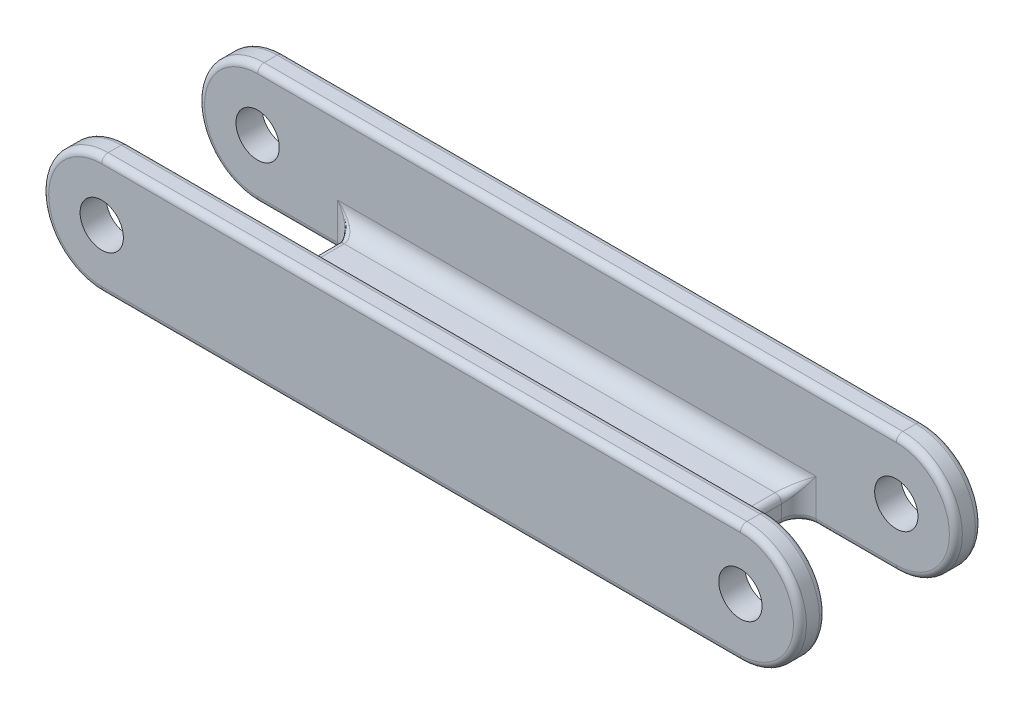
SolidWorks part; units mm, degrees
material "AISI 1020"
ref_plane "Front Plane" through (0, 0, 0) normal (0, 0, 1) x (1, 0, 0)
ref_plane "Top Plane" through (0, 0, 0) normal (0, 1, 0) x (1, 0, 0)
ref_plane "Right Plane" through (0, 0, 0) normal (1, 0, 0) x (0, 0, -1)
sketch "Sketch1" plane through (0, 0, 0) normal (1, 0, 0) x (0, 0, -1)
  line L0 (-42, 27.5) -> (-30, 27.5)
  line L1 (42, -27.5) -> (-42, -27.5)
  line L2 (42, -27.5) -> (42, 27.5)
  line L3 (42, 27.5) -> (-42, 27.5) construction
  line L4 (-42, -27.5) -> (-42, 27.5)
  line L5 (42, -27.5) -> (-42, 27.5) construction
  line L6 (42, 27.5) -> (-42, -27.5) construction
  line L7 (-30, 27.5) -> (-30, -15.5)
  line L8 (-30, -15.5) -> (30, -15.5)
  line L9 (30, -15.5) -> (30, 27.5)
  line L10 (30, 27.5) -> (42, 27.5)
  point P0 (0, 0)
  dimension "D1" = 12
  dimension "D2" = 12
  dimension "D3" = 60
  dimension "D4" = 55
extrude "Boss-Extrude1" add sketch "Sketch1" along normal blind 350
sketch "Sketch2" plane through (0, 0, 0) normal (0, 0, 1) x (1, 0, 0)
  line L0 (350, 27.5) -> (350, -27.5) construction
  line L1 (350, -27.5) -> (0, -27.5) construction
  line L2 (350, 27.5) -> (0, 27.5) construction
  line L3 (0, 27.5) -> (0, -27.5) construction
  line L4 (27.5, 27.5) -> (0, 27.5)
  line L5 (0, 27.5) -> (0, -27.5)
  line L6 (0, -27.5) -> (27.5, -27.5)
  line L7 (322.5, 27.5) -> (350, 27.5)
  line L8 (350, 27.5) -> (350, -27.5)
  line L9 (350, -27.5) -> (322.5, -27.5)
  circle A0 centre (27.5, 0) radius 10
  circle A1 centre (27.5, 0) radius 27.5
  circle A2 centre (322.5, 0) radius 27.5
  circle A3 centre (322.5, 0) radius 10
  dimension "D1" = 20
extrude "Cut-Extrude1" cut sketch "Sketch2" against normal through all both and the other way through all contours A1 L4 L5 | A1 L5 L6 | A0 | A3 | A2 L8 L7 | A2 L9 L8 region at (6.1426, 21.3574, 0) region at (6.1426, -21.3574, 0) region at (343.8574, 21.3574, 0) region at (343.8574, -21.3574, 0) region at (27.5, 0, 0) region at (322.5, 0, 0)
sketch "Sketch3" plane through (0, 0, 42) normal (0, 0, 1) x (1, 0, 0)
  line L0 (4.7844, -15.5) -> (345.2156, -15.5)
  line L1 (322.5, -27.5) -> (27.5, -27.5) construction
  line L2 (322.5, -27.5) -> (27.5, -27.5)
  line L3 (345.2156, -15.5) -> (4.7844, -15.5) construction
  line L4 (72.5, -15.5) -> (72.5, -27.5)
  line L5 (277.5, -15.5) -> (277.5, -27.5)
  arc A0 (27.5, 27.5) -> (27.5, -27.5) centre (27.5, 0) ccw construction
  arc A1 (322.5, -27.5) -> (322.5, 27.5) centre (322.5, 0) ccw construction
  arc A2 (4.7844, -15.5) -> (27.5, -27.5) centre (27.5, 0) ccw
  arc A3 (322.5, -27.5) -> (345.2156, -15.5) centre (322.5, 0) ccw
  arc M4 (27.5, 27.5) -> (27.5, -27.5) centre (27.5, 0) ccw
  line M5 (27.5, -27.5) -> (322.5, -27.5)
  arc M6 (322.5, -27.5) -> (322.5, 27.5) centre (322.5, 0) ccw
  dimension "D1" = 45
  dimension "D2" = 45
extrude "Cut-Extrude2" cut sketch "Sketch3" against normal up to surface (72 mm away) from surface contours L4 L0 M4 M5 | L0 L5 M5 M6 region at (41.7967, -21.2128, 42) region at (308.2033, -21.2128, 42) up to face at (17.5, 0, -30) starting at face at (27.5, -10, 30)
fillet "Fillet2" radius 8 6 edges at (175, -15.5, 30) (175, -15.5, -30) (277.5, -21.5, 30) (277.5, -21.5, -30) (72.5, -21.5, 30) (72.5, -21.5, -30)
fillet "Fillet1" radius 3 30 edges at (350, 0, -42) (175, -27.5, -42) (0, 0, -42) (350, 0, -30) (0, 0, -30) (0, 0, 30) (175, 27.5, 30) (175, -27.5, 42) (0, 0, 42) (175, 27.5, 42) (175, 27.5, -42) (175, 27.5, -30) (350, 0, 30) (350, 0, 42) (304, -27.5, -30) (46, -27.5, -30) (304, -27.5, 30) (46, -27.5, 30) (279.8431, -27.5, 27.6569) (277.5, -27.5, 0) (279.8431, -27.5, -27.6569) (70.1569, -27.5, -27.6569) (72.5, -27.5, 0) (70.1569, -27.5, 27.6569) (279.8431, -13.1569, -27.6569) (279.8431, -13.1569, 27.6569) (70.1569, -13.1569, -27.6569) (70.1569, -13.1569, 27.6569) (277.5, -15.5, 0) (72.5, -15.5, 0)
